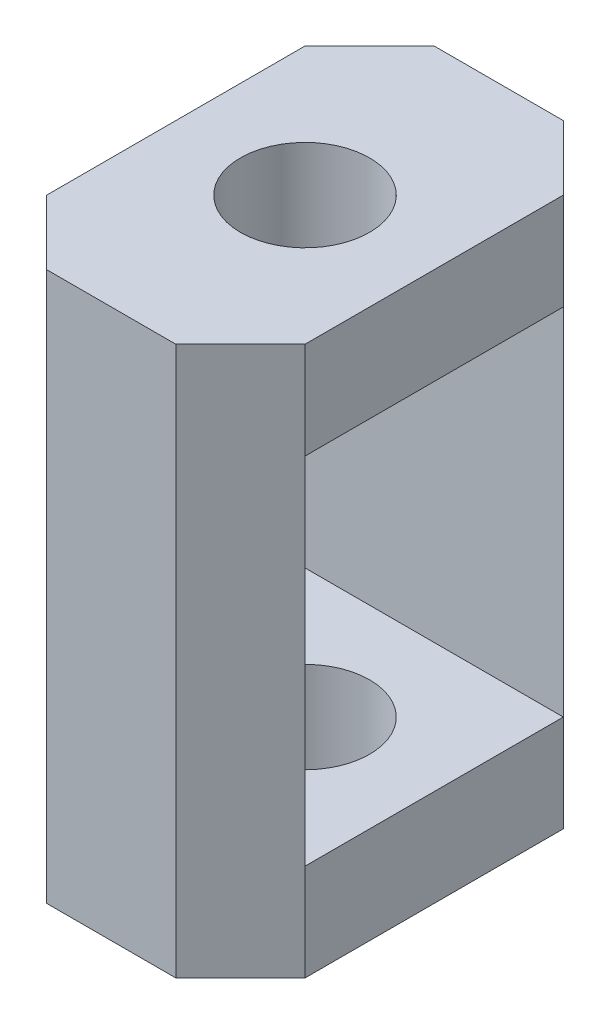
SolidWorks part; units mm, degrees
material "Plain Carbon Steel"
ref_plane "Front Plane" through (0, 0, 0) normal (0, 0, 1) x (1, 0, 0)
ref_plane "Top Plane" through (0, 0, 0) normal (0, 1, 0) x (1, 0, 0)
ref_plane "Right Plane" through (0, 0, 0) normal (1, 0, 0) x (0, 0, -1)
sketch "Sketch1" plane through (0, 0, 0) normal (0, 1, 0) x (1, 0, 0)
  line L1 (-4, -6) -> (4, -6)
  line L2 (-4, -6) -> (-4, 6)
  line L3 (-4, 6) -> (4, 6)
  line L4 (4, -6) -> (4, 6)
  line L5 (-4, -6) -> (4, 6) construction
  line L6 (-4, 6) -> (4, -6) construction
  circle A0 centre (0, 0) radius 2
  point P0 (0, 0)
  dimension "D1" = 4
  dimension "D2" = 8
  dimension "D3" = 12
extrude "Boss-Extrude1" add sketch "Sketch1" along normal blind 17
sketch "Sketch2" plane through (4, 0, 0) normal (1, 0, 0) x (0, 0, -1)
  line L0 (-6, 0) -> (6, 0) construction
  line L1 (-4, 3) -> (4, 3)
  line L2 (-4, 3) -> (-4, 14)
  line L3 (-4, 14) -> (4, 14)
  line L4 (4, 3) -> (4, 14)
  line L5 (-4, 3) -> (4, 14) construction
  line L6 (-4, 14) -> (4, 3) construction
  line L7 (-6, 17) -> (-6, 0) construction
  line L8 (-6, 17) -> (6, 17) construction
  line L9 (6, 17) -> (6, 0) construction
  point P0 (0, 8.5)
  dimension "D1" = 3
  dimension "D2" = 2
  dimension "D3" = 3
  dimension "D4" = 2
extrude "Cut-Extrude1" cut sketch "Sketch2" against normal blind 17
chamfer "Chamfer1" distance 2 angle 45 4 edges at (-4, 8.5, 6) (-4, 8.5, -6) (4, 8.5, -6) (4, 8.5, 6)
